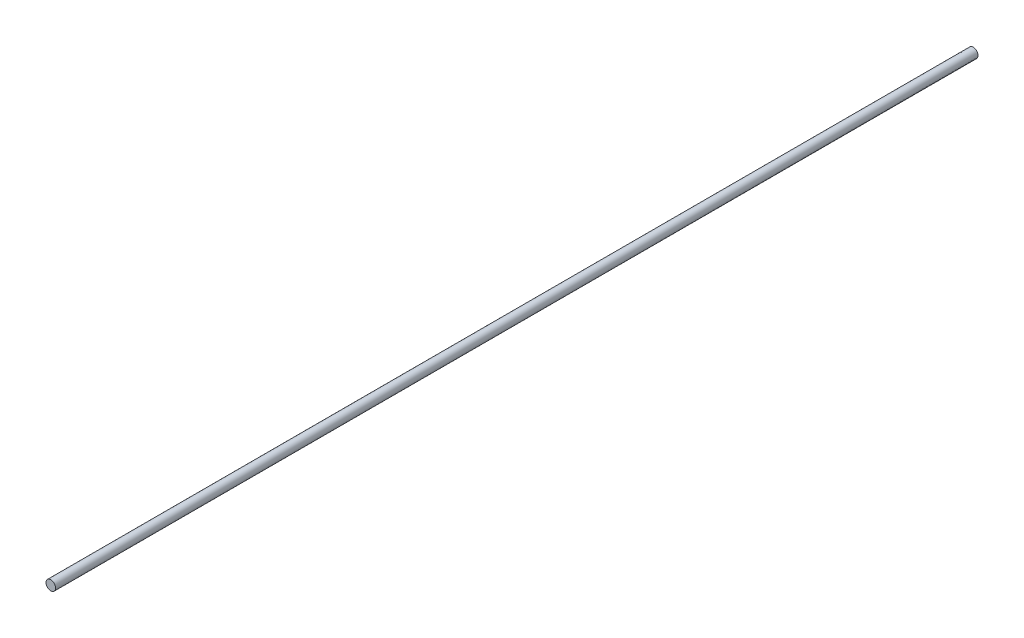
SolidWorks part; units mm, degrees
ref_plane "Front Plane" through (0, 0, 0) normal (0, 0, 1) x (1, 0, 0)
ref_plane "Top Plane" through (0, 0, 0) normal (0, 1, 0) x (1, 0, 0)
ref_plane "Right Plane" through (0, 0, 0) normal (1, 0, 0) x (0, 0, -1)
sketch "Sketch1" plane through (0, 0, 0) normal (0, 0, 1) x (1, 0, 0)
  circle A0 centre (0, 0) radius 3.175
  dimension "D1" = 6.35
extrude "Boss-Extrude1" add sketch "Sketch1" along normal blind 609.6
